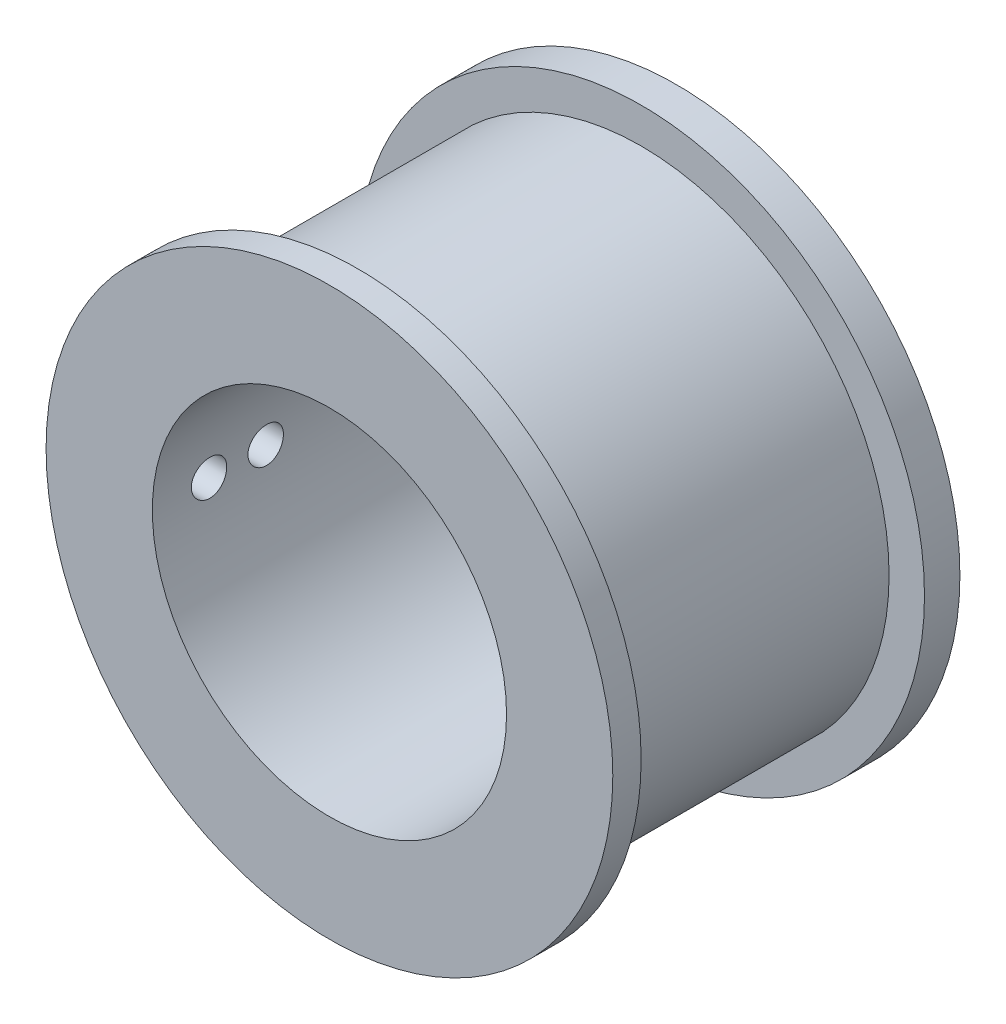
SolidWorks part; units mm, degrees
ref_plane "Front Plane" through (0, 0, 0) normal (0, 0, 1) x (1, 0, 0)
ref_plane "Top Plane" through (0, 0, 0) normal (0, 1, 0) x (1, 0, 0)
ref_plane "Right Plane" through (0, 0, 0) normal (1, 0, 0) x (0, 0, -1)
sketch "Sketch1" plane through (0, 0, 0) normal (0, 0, 1) x (1, 0, 0)
  circle A0 centre (0, 0) radius 25.4
  circle A1 centre (0, 0) radius 8.001 construction
  circle A2 centre (0, -8.001) radius 1.7
  circle A3 centre (0, 8.001) radius 1.7
  circle A4 centre (-6.9291, 4.0005) radius 1.7
  arc A5 (0, 8.001) -> (-6.9291, 4.0005) centre (0, 0) ccw construction
  circle A6 centre (-6.9291, -4.0005) radius 1.7
  circle A7 centre (6.9291, -4.0005) radius 1.7
  circle A8 centre (6.9291, 4.0005) radius 1.7
  dimension "D1" = 50.8
  dimension "D2" = 16.002
  dimension "D9" = 3.4
  dimension "D5" = 60
extrude "Boss-Extrude1" add sketch "Sketch1" along normal blind 3.175
sketch "Sketch4" plane through (0, 0, 3.175) normal (0, 0, 1) x (1, 0, 0)
  circle A0 centre (0, 0) radius 22.225
  circle A1 centre (0, 0) radius 15.875
  circle A2 centre (-6.9291, 4.0005) radius 3.25 construction
  dimension "D1" = 44.45
  dimension "D2" = 31.75
  dimension "D3" = 6.5
extrude "Boss-Extrude2" add sketch "Sketch4" along normal blind 25.4
sketch "Sketch5" plane through (0, 0, 28.575) normal (0, 0, 1) x (1, 0, 0)
  circle A0 centre (0, 0) radius 25.4
  circle A1 centre (0, 0) radius 15.875
extrude "Boss-Extrude3" add sketch "Sketch5" along normal blind 2.54
sketch "Sketch6" plane through (0, 0, 0) normal (1, 0, 0) x (0, 0, -1)
  line L0 (-28.575, -25.4) -> (-28.575, 25.4) construction
  circle A0 centre (-26.035, 0) radius 1.5875
  circle A1 centre (-20.955, 0) radius 1.5875
  dimension "D1" = 3.175
  dimension "D2" = 2.54
  dimension "D3" = 5.08
extrude "Cut-Extrude1" cut sketch "Sketch6" against normal through all
